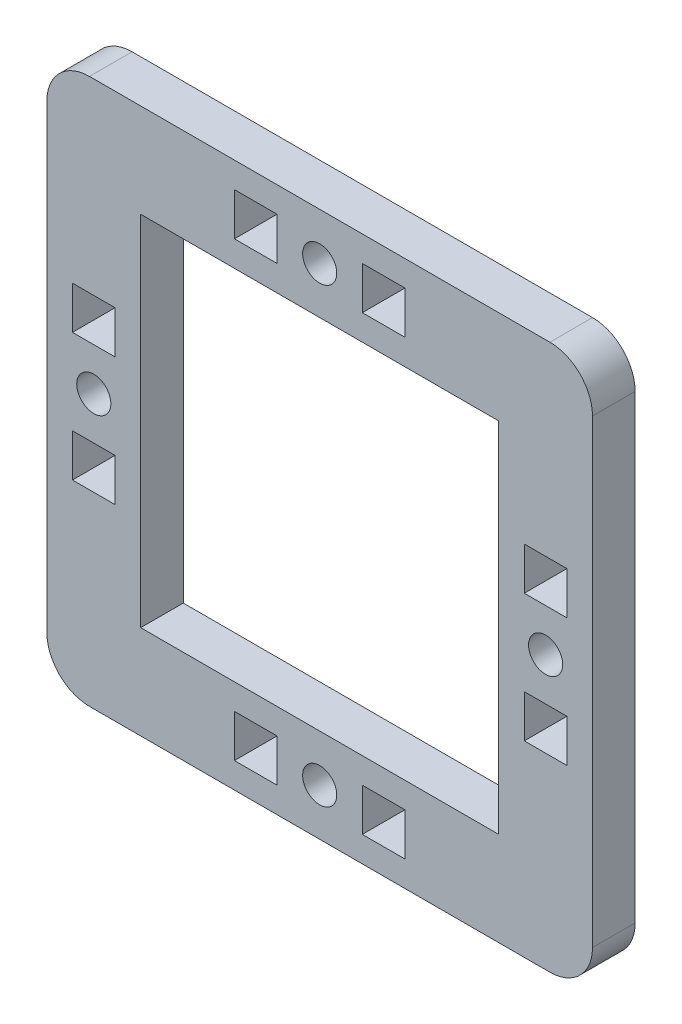
SolidWorks part; units mm, degrees
ref_plane "Plan de face" through (0, 0, 0) normal (0, 0, 1) x (1, 0, 0)
ref_plane "Plan de dessus" through (0, 0, 0) normal (0, 1, 0) x (1, 0, 0)
ref_plane "Plan de droite" through (0, 0, 0) normal (1, 0, 0) x (0, 0, -1)
sketch "Esquisse1" plane through (0, 0, 0) normal (0, 0, 1) x (1, 0, 0)
  line L0 (-24, 24) -> (24, 24) construction
  line L1 (24, 24) -> (24, -24) construction
  line L2 (24, -24) -> (-24, -24) construction
  line L3 (-24, -24) -> (-24, 24) construction
  line L4 (0, 0) -> (0, 24) construction
  line L5 (0, 0) -> (24, 0) construction
  line L6 (-21, 21) -> (21, 21)
  line L7 (21, 21) -> (21, -21)
  line L8 (21, -21) -> (-21, -21)
  line L9 (-21, -21) -> (-21, 21)
  line L10 (-32, 32) -> (32, 32)
  line L11 (32, 32) -> (32, -32)
  line L12 (32, -32) -> (-32, -32)
  line L13 (-32, -32) -> (-32, 32)
  point P16 (0, 0)
  point P17 (0, 0)
  point P18 (19.7186, 21)
  point P19 (0, 0)
  point P20 (0, 0)
  line B0 (29, 5) -> (29, 10)
  line B1 (29, 5) -> (24, 5)
  line B2 (24, 5) -> (24, 10)
  line B3 (29, 10) -> (24, 10)
  line B4 (29, -5) -> (29, -10)
  line B5 (29, -5) -> (24, -5)
  line B6 (24, -5) -> (24, -10)
  line B7 (29, -10) -> (24, -10)
  line B8 (26.5, 0) -> (33.4724, 0) construction
  circle B9 centre (26.5, 0) radius 2
  line B10 (-29, 5) -> (-29, 10)
  line B11 (-29, 5) -> (-24, 5)
  line B12 (-24, 5) -> (-24, 10)
  line B13 (-29, 10) -> (-24, 10)
  line B14 (-29, -5) -> (-29, -10)
  line B15 (-29, -5) -> (-24, -5)
  line B16 (-24, -5) -> (-24, -10)
  line B17 (-29, -10) -> (-24, -10)
  circle B18 centre (-26.5, 0) radius 2
  line B19 (5, 29) -> (10, 29)
  line B20 (5, 29) -> (5, 24)
  line B21 (5, 24) -> (10, 24)
  line B22 (10, 29) -> (10, 24)
  line B23 (-5, 29) -> (-10, 29)
  line B24 (-5, 29) -> (-5, 24)
  line B25 (-5, 24) -> (-10, 24)
  line B26 (-10, 29) -> (-10, 24)
  line B27 (0, 26.5) -> (0, 33.4724) construction
  circle B28 centre (0, 26.5) radius 2
  line B29 (5, -29) -> (10, -29)
  line B30 (5, -29) -> (5, -24)
  line B31 (5, -24) -> (10, -24)
  line B32 (10, -29) -> (10, -24)
  line B33 (-5, -29) -> (-10, -29)
  line B34 (-5, -29) -> (-5, -24)
  line B35 (-5, -24) -> (-10, -24)
  line B36 (-10, -29) -> (-10, -24)
  circle B37 centre (0, -26.5) radius 2
  dimension "D1" = 48
  dimension "D2" = 180
  dimension "D3" = 3
  dimension "D4" = 64
  dimension "D5" = 64
  dimension "D6" = 3
  dimension "D7" = 42
  dimension "D8" = 42
sketch_block_instance "Trou M4 plots 5mm-1"
sketch_block "Trou M4 plots 5mm" parameters "D2"=4, "D1"=5, "D3"=5, "D4"=10
sketch_block_instance "Trou M4 plots 5mm-3"
sketch_block_instance "Trou M4 plots 5mm-4"
sketch_block_instance "Trou M4 plots 5mm-5"
extrude "Boss.-Extru.1" add sketch "Esquisse1" along normal blind 5
fillet "Congé1" radius 5 4 edges at (32, -32, 2.5) (-32, -32, 2.5) (-32, 32, 2.5) (32, 32, 2.5)
